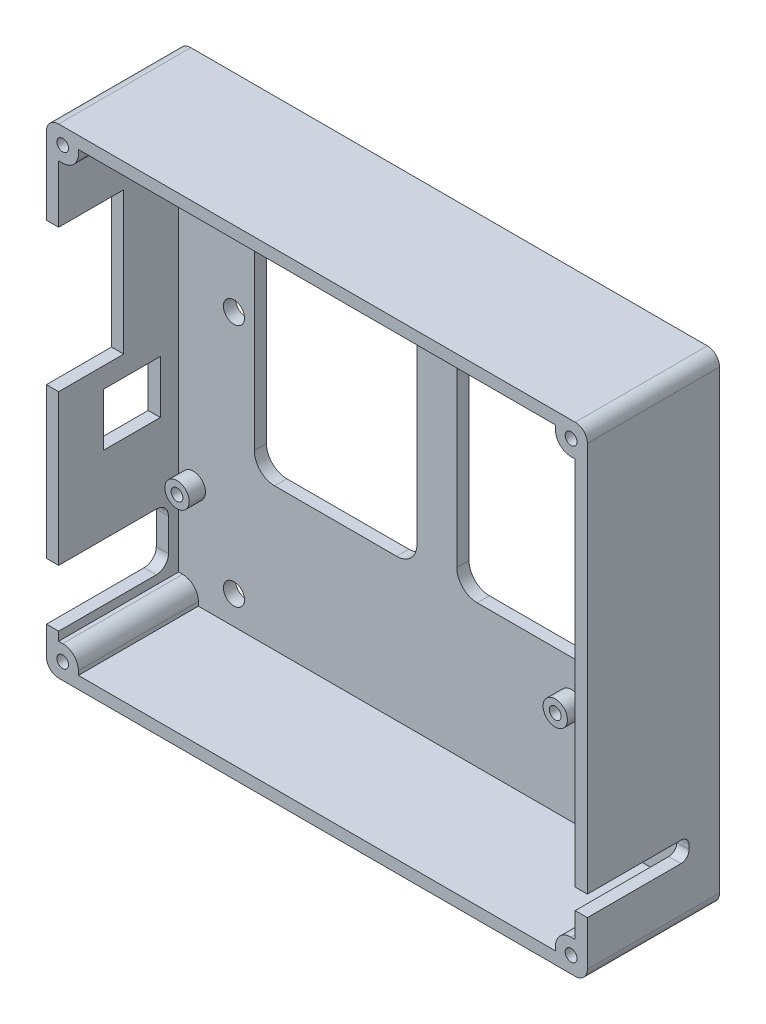
SolidWorks part; units mm, degrees
material "ABS"
ref_plane "Front Plane" through (0, 0, 0) normal (0, 0, 1) x (1, 0, 0)
ref_plane "Top Plane" through (0, 0, 0) normal (0, 1, 0) x (1, 0, 0)
ref_plane "Right Plane" through (0, 0, 0) normal (1, 0, 0) x (0, 0, -1)
sketch "Sketch1" plane through (0, 0, 0) normal (0, 0, 1) x (1, 0, 0)
  line L0 (-63.5, -56) -> (-63.5, 56) construction
  line L1 (-63.5, -59) -> (63.5, -59)
  line L2 (-66.5, -56) -> (-66.5, 56)
  line L3 (-63.5, 59) -> (63.5, 59)
  line L4 (66.5, -56) -> (66.5, 56)
  line L5 (-66.5, -59) -> (66.5, 59) construction
  line L6 (-66.5, 59) -> (66.5, -59) construction
  line L7 (44.9, 26) -> (44.9, -16)
  line L8 (63.5, -51.15) -> (63.5, 51.15)
  line L9 (-63.5, -51.15) -> (-63.5, 51.15)
  line L10 (-58.65, 55) -> (-58.65, 56)
  line L11 (-62.5, 51.15) -> (-63.5, 51.15)
  line L12 (-58.65, 56) -> (58.65, 56)
  line L13 (-63.5, 56) -> (63.5, 56) construction
  line L14 (0, 59) -> (0, -59) construction
  line L15 (-66.5, 0) -> (66.5, 0) construction
  line L16 (62.5, 51.15) -> (63.5, 51.15)
  line L17 (58.65, 55) -> (58.65, 56)
  line L18 (63.5, -56) -> (63.5, 56) construction
  line L19 (58.65, -55) -> (58.65, -56)
  line L20 (62.5, -51.15) -> (63.5, -51.15)
  line L21 (-62.5, -51.15) -> (-63.5, -51.15)
  line L22 (-58.65, -55) -> (-58.65, -56)
  line L23 (-58.65, -56) -> (58.65, -56)
  line L24 (-63.5, -56) -> (63.5, -56) construction
  line L25 (-39.9, 31) -> (-9.9, 31)
  line L26 (-44.9, 26) -> (-44.9, -16)
  line L27 (-39.9, -21) -> (-9.9, -21)
  line L28 (-4.9, 26) -> (-4.9, -16)
  line L29 (-44.9, 31) -> (-4.9, -21) construction
  line L30 (-44.9, -21) -> (-4.9, 31) construction
  line L31 (39.9, -21) -> (9.9, -21)
  line L32 (4.9, 26) -> (4.9, -16)
  line L33 (39.9, 31) -> (9.9, 31)
  line L35 (-59.9, -30.875) -> (33.1, -30.875) construction
  line L36 (-59.9, -30.875) -> (-59.9, 40.875) construction
  line L37 (-59.9, 40.875) -> (33.1, 40.875) construction
  line L38 (33.1, -30.875) -> (33.1, 40.875) construction
  line L39 (-59.9, -30.875) -> (33.1, 40.875) construction
  line L40 (-59.9, 40.875) -> (33.1, -30.875) construction
  arc A0 (63.5, 59) -> (66.5, 56) centre (63.5, 56) cw
  arc A1 (66.5, -56) -> (63.5, -59) centre (63.5, -56) cw
  arc A2 (-63.5, -59) -> (-66.5, -56) centre (-63.5, -56) cw
  arc A3 (-66.5, 56) -> (-63.5, 59) centre (-63.5, 56) cw
  arc A4 (63.5, 56) -> (63.5, 56) centre (63.5, 56) cw
  arc A5 (-9.9, 31) -> (-4.9, 26) centre (-9.9, 26) cw
  arc A6 (-63.5, -56) -> (-63.5, -56) centre (-63.5, -56) cw
  arc A7 (-63.5, 56) -> (-63.5, 56) centre (-63.5, 56) cw
  circle A8 centre (-62.5, 55) radius 1.45
  arc A9 (-62.5, 51.15) -> (-58.65, 55) centre (-62.5, 55) ccw
  circle A10 centre (-62.5, 55) radius 3.85 construction
  circle A11 centre (62.5, 55) radius 1.45
  arc A12 (62.5, 51.15) -> (58.65, 55) centre (62.5, 55) cw
  circle A13 centre (62.5, -55) radius 1.45
  arc A14 (62.5, -51.15) -> (58.65, -55) centre (62.5, -55) ccw
  circle A15 centre (-62.5, -55) radius 1.45
  arc A16 (-62.5, -51.15) -> (-58.65, -55) centre (-62.5, -55) cw
  arc A17 (63.5, -56) -> (63.5, -56) centre (63.5, -56) cw construction
  arc A18 (-4.9, -16) -> (-9.9, -21) centre (-9.9, -16) cw
  arc A19 (-39.9, -21) -> (-44.9, -16) centre (-39.9, -16) cw
  arc A20 (-44.9, 26) -> (-39.9, 31) centre (-39.9, 26) cw
  arc A21 (39.9, -21) -> (44.9, -16) centre (39.9, -16) ccw
  arc A22 (4.9, -16) -> (9.9, -21) centre (9.9, -16) ccw
  arc A23 (9.9, 31) -> (4.9, 26) centre (9.9, 26) ccw
  arc A24 (44.9, 26) -> (39.9, 31) centre (39.9, 26) ccw
  circle A25 centre (-59.9, 40.875) radius 1.45
  circle A26 centre (33.1, 40.875) radius 1.45
  circle A27 centre (33.1, -30.875) radius 1.45
  circle A28 centre (-59.9, -30.875) radius 1.45
  circle A29 centre (-59.9, 40.875) radius 3
  circle A30 centre (33.1, 40.875) radius 3
  circle A31 centre (33.1, -30.875) radius 3
  circle A32 centre (-59.9, -30.875) radius 3
  circle A33 centre (-49.9, 11) radius 2.6
  circle A34 centre (51.5, 11) radius 2.6
  circle A35 centre (-49.9, -49) radius 2.6
  circle A36 centre (51.5, -49) radius 2.6
  point P0 (0, 0)
  point P60 (-24.9, 5)
  point P89 (-13.4, 5)
  dimension "D3" = 3
  dimension "D5" = 110
  dimension "D7" = 2.9
  dimension "D8" = 40
  dimension "D4" = 125
  dimension "D10" = 5
  dimension "D13" = 2.9
  dimension "D16" = 6
  dimension "D17" = 3.6
  dimension "D18" = 5.2
  dimension "D19" = 101.4
  dimension "D20" = 60
  dimension "D21" = 10
  dimension "D23" = 12
  dimension "D1" = 133
  dimension "D2" = 118
  dimension "D9" = 52
  dimension "D11" = 9.8
  dimension "D12" = 28
  dimension "D14" = 93
  dimension "D15" = 71.75
  dimension "D6" = 2.4
extrude "Boss-Extrude1" add sketch "Sketch1" against normal blind 3 contours L1 A1 L4 A0 L3 A3 L2 A2 | L26 A19 L27 A18 L28 A5 L25 A20 | L32 A22 L31 A21 L7 A24 L33 A23 | A33 | A35 | A36 | A34 | A26 | A25 | A28 | A27
extrude "Boss-Extrude2" add sketch "Sketch1<3>" along normal blind 29.5 contours A3 L2 A2 L1 A1 L4 A0 L3 A16 L21 L9 L11 A9 L10 L12 L17 A12 L16 L8 L20 A14 L19 L23 L22 A11 A8 A13 A15 region at (-64.3641, -56.8641, 0)
sketch "Sketch1<3>" plane through (0, 0, 0) normal (0, 0, 1) x (1, 0, 0) same geometry as "Sketch1"
extrude "Boss-Extrude3" add sketch "Sketch1<4>" along normal blind 4 contours A29 A25 | A30 A26 | A31 A27 | A32 A28 region at (-62.8151, 40.875, 0) region at (30.1849, 40.875, 0) region at (30.1849, -30.875, 0) region at (-62.8151, -30.875, 0)
sketch "Sketch1<4>" plane through (0, 0, 0) normal (0, 0, 1) x (1, 0, 0) same geometry as "Sketch1"
sketch "Sketch5" plane through (-66.5, 0, 0) normal (-1, 0, 0) x (0, 0, 1)
  line L0 (29.5, -56) -> (29.5, 56) construction
  line L3 (-3, -59) -> (29.5, -59) construction
  line L4 (4.5, -16) -> (18.5, -16)
  line L5 (-3, 59) -> (29.5, 59) construction
  line L16 (29.5, -35) -> (5.5, -35)
  line L17 (2.5, -38) -> (2.5, -46)
  line L18 (5.5, -49) -> (29.5, -49)
  line L19 (29.5, 37) -> (13.5, 37)
  line L20 (13.5, 2) -> (29.5, 2)
  line L21 (29.5, 2) -> (29.5, 37)
  line L22 (29.5, -49) -> (29.5, -35)
  line L23 (4.5, -3) -> (18.5, -3)
  line L24 (4.5, -3) -> (4.5, -16)
  line L25 (18.5, -3) -> (18.5, -16)
  line L26 (13.5, 37) -> (13.5, 2)
  arc A2 (5.5, -49) -> (2.5, -46) centre (5.5, -46) cw
  arc A3 (2.5, -38) -> (5.5, -35) centre (5.5, -38) cw
  dimension "D7" = 5
  dimension "D3" = 3
  dimension "D1" = 14
  dimension "D2" = 27
  dimension "D4" = 13
  dimension "D5" = 14
  dimension "D6" = 11
  dimension "D8" = 16
  dimension "D9" = 35
  dimension "D10" = 10
  dimension "D11" = 22
extrude "Cut-Extrude2" cut sketch "Sketch5" against normal up to surface (3 mm away) up to face at (-63.5, 0, 14.75)
sketch "Lid Model For Reference" plane through (0, 0, 29.5) normal (0, 0, 1) x (1, 0, 0)
  line L0 (0, 0) -> (66.5, 0) construction
  line L40 (0, 59) -> (0, -59) construction
  line L41 (3.5, 14) -> (-28.5, -18) construction
  line L42 (3.5, -18) -> (-28.5, 14) construction
  line L43 (-28.5, -18) -> (-28.5, 14) construction
  line L44 (3.5, 14) -> (-28.5, 14) construction
  line L45 (3.5, -18) -> (3.5, 14) construction
  line L46 (3.5, -18) -> (-28.5, -18) construction
  line L47 (66.5, 59) -> (-66.5, -59) construction
  line L48 (66.5, -59) -> (-66.5, 59) construction
  line L49 (-66.5, -27) -> (-66.5, -9)
  line L50 (-66.5, 26) -> (-66.5, 56)
  line L51 (-50.5, -40) -> (-66.5, -40)
  line L52 (-50.5, -27) -> (-50.5, -40)
  line L53 (-66.5, -27) -> (-50.5, -27)
  line L54 (-50.5, -9) -> (-66.5, -9)
  line L55 (-50.5, 26) -> (-50.5, -9)
  line L56 (-66.5, 26) -> (-50.5, 26)
  line L57 (55.75, -12.5) -> (27.75, -12.5)
  line L58 (55.75, -7.5) -> (27.75, -7.5)
  line L59 (55.75, -22.5) -> (27.75, -22.5)
  line L60 (55.75, -17.5) -> (27.75, -17.5)
  line L61 (55.75, -32.5) -> (27.75, -32.5)
  line L62 (55.75, -27.5) -> (27.75, -27.5)
  line L63 (55.75, -42.5) -> (27.75, -42.5)
  line L64 (55.75, -37.5) -> (27.75, -37.5)
  line L65 (55.75, 37.5) -> (27.75, 37.5)
  line L66 (55.75, 42.5) -> (27.75, 42.5)
  line L67 (55.75, 27.5) -> (27.75, 27.5)
  line L68 (55.75, 32.5) -> (27.75, 32.5)
  line L69 (55.75, 17.5) -> (27.75, 17.5)
  line L70 (55.75, 22.5) -> (27.75, 22.5)
  line L71 (55.75, 7.5) -> (27.75, 7.5)
  line L72 (55.75, 12.5) -> (27.75, 12.5)
  line L73 (55.75, -2.5) -> (27.75, -2.5)
  line L74 (55.75, 2.5) -> (27.75, 2.5)
  line L75 (-66.5, -56) -> (-66.5, -40)
  line L76 (63.5, 59) -> (-63.5, 59)
  line L77 (66.5, -56) -> (66.5, 56)
  line L78 (63.5, -59) -> (-63.5, -59)
  arc A5 (55.75, -2.5) -> (55.75, 2.5) centre (55.75, 0) ccw
  arc A6 (27.75, 2.5) -> (27.75, -2.5) centre (27.75, 0) ccw
  circle A31 centre (-62.5, -55) radius 1.6
  circle A32 centre (62.5, -55) radius 1.6
  circle A33 centre (-62.5, 55) radius 1.6
  circle A34 centre (62.5, 55) radius 1.6
  arc A35 (66.5, 56) -> (63.5, 59) centre (63.5, 56) ccw
  arc A36 (63.5, -59) -> (66.5, -56) centre (63.5, -56) ccw
  arc A37 (-66.5, -56) -> (-63.5, -59) centre (-63.5, -56) ccw
  arc A38 (-63.5, 59) -> (-66.5, 56) centre (-63.5, 56) ccw
  arc A39 (55.75, -12.5) -> (55.75, -7.5) centre (55.75, -10) ccw
  arc A40 (27.75, -7.5) -> (27.75, -12.5) centre (27.75, -10) ccw
  arc A41 (55.75, -22.5) -> (55.75, -17.5) centre (55.75, -20) ccw
  arc A42 (27.75, -17.5) -> (27.75, -22.5) centre (27.75, -20) ccw
  arc A43 (55.75, -32.5) -> (55.75, -27.5) centre (55.75, -30) ccw
  arc A44 (27.75, -27.5) -> (27.75, -32.5) centre (27.75, -30) ccw
  arc A45 (55.75, -42.5) -> (55.75, -37.5) centre (55.75, -40) ccw
  arc A46 (27.75, -37.5) -> (27.75, -42.5) centre (27.75, -40) ccw
  arc A47 (27.75, 37.5) -> (27.75, 42.5) centre (27.75, 40) cw
  arc A48 (55.75, 42.5) -> (55.75, 37.5) centre (55.75, 40) cw
  arc A49 (27.75, 27.5) -> (27.75, 32.5) centre (27.75, 30) cw
  arc A50 (55.75, 32.5) -> (55.75, 27.5) centre (55.75, 30) cw
  arc A51 (27.75, 17.5) -> (27.75, 22.5) centre (27.75, 20) cw
  arc A52 (55.75, 22.5) -> (55.75, 17.5) centre (55.75, 20) cw
  arc A53 (27.75, 7.5) -> (27.75, 12.5) centre (27.75, 10) cw
  arc A54 (55.75, 12.5) -> (55.75, 7.5) centre (55.75, 10) cw
  circle A55 centre (3.5, -18) radius 1.6
  circle A56 centre (-28.5, -18) radius 1.6
  circle A57 centre (-28.5, 14) radius 1.6
  circle A58 centre (3.5, 14) radius 1.6
  circle A59 centre (-12.5, -2) radius 18
  point P0 (0, 0)
  point P21 (-12.5, 2)
  dimension "D8" = 5
  dimension "D9" = 28
sketch "Sketch6" plane through (66.5, 0, 0) normal (1, 0, 0) x (0, 0, -1)
  line L1 (-6.5, -45) -> (-29.5, -45)
  line L2 (-4.5, -43) -> (-4.5, -42)
  line L3 (-6.5, -40) -> (-29.5, -40)
  line L4 (-29.5, -45) -> (-29.5, -40)
  line L5 (-29.5, -49) -> (-5.5, -49) construction
  line L6 (-29.5, -56) -> (-29.5, 56) construction
  arc A0 (-6.5, -40) -> (-4.5, -42) centre (-6.5, -42) cw
  arc A1 (-4.5, -43) -> (-6.5, -45) centre (-6.5, -43) cw
  dimension "D2" = 2
  dimension "D1" = 5
  dimension "D3" = 25
  dimension "D4" = 4
extrude "Cut-Extrude3" cut sketch "Sketch6" against normal up to next contours L3 L4 L1 A1 L2 A0
